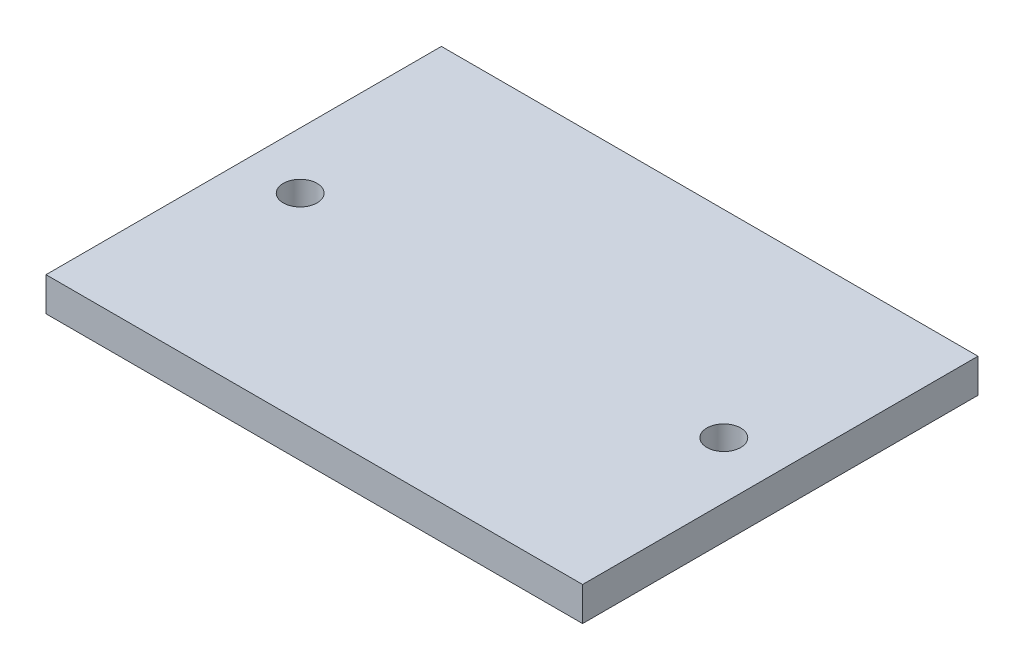
SolidWorks part; units mm, degrees
ref_plane "Front Plane" through (0, 0, 0) normal (0, 0, 1) x (1, 0, 0)
ref_plane "Top Plane" through (0, 0, 0) normal (0, 1, 0) x (1, 0, 0)
ref_plane "Right Plane" through (0, 0, 0) normal (1, 0, 0) x (0, 0, -1)
sketch "Sketch2" plane through (0, 0, 0) normal (0, 1, 0) x (1, 0, 0)
  line L1 (0, 0) -> (47.5, 0)
  line L2 (0, 0) -> (0, 35)
  line L3 (0, 35) -> (47.5, 35)
  line L4 (47.5, 0) -> (47.5, 35)
  dimension "D1" = 47.5
  dimension "D2" = 35
extrude "Boss-Extrude1" add sketch "Sketch2" along normal blind 3
hole_wizard "Ø3.0mm Dowel Hole1" positions "Sketch3" profile "Sketch4" hole size "Ø3.0" standard "ANSI Metric" end condition up to next
sketch "Sketch3" plane through (0, 3, 0) normal (0, 1, 0) x (1, 0, 0)
  line L0 (0, 17.5) -> (47.5, 17.5) construction
  line L1 (0, 35) -> (0, 0) construction
  line L2 (47.5, 0) -> (47.5, 35) construction
  line L4 (47.5, 35) -> (0, 35) construction
  point P0 (5, 17.5)
  point P2 (42.5, 17.5)
  point P15 (0, 0)
  point P16 (0, 0)
  dimension "D1" = 17.5
  dimension "D2" = 5
  dimension "D3" = 5
sketch "Sketch4" plane through (5, 3, -17.5) normal (1, 0, 0) x (0, 0, 1)
  line L0 (0, 0) -> (0, 3)
  line L1 (0, 3) -> (1.5, 3)
  line L2 (1.5, 3) -> (1.5, 0)
  line L5 (1.5, 0) -> (0, 0)
  line L11 (0, -6.35) -> (0, 107.95) construction
  dimension "Thru Hole Dia." = 3
  dimension "Thru Hole Depth" = 3
